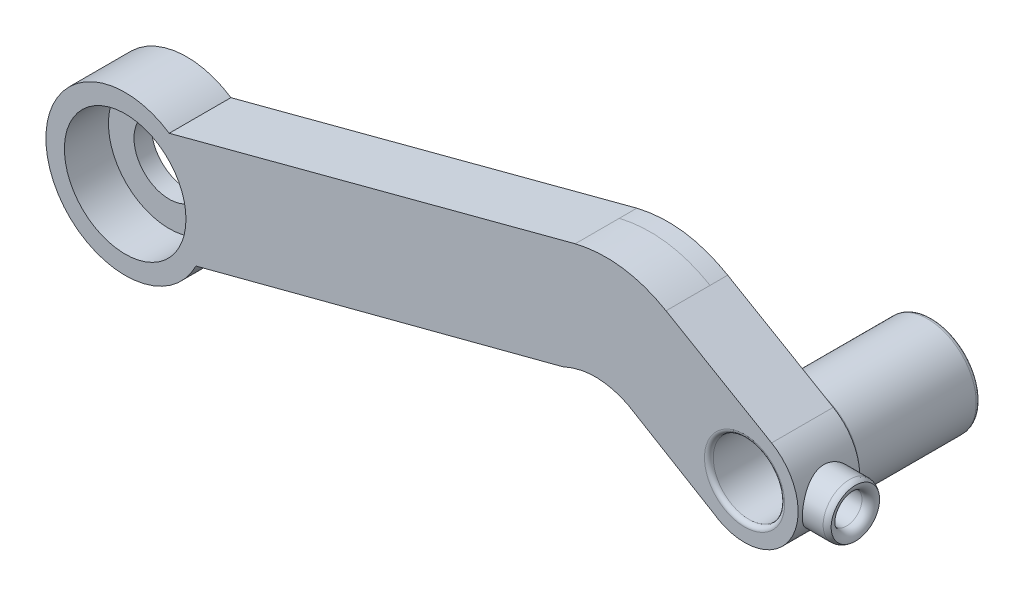
SolidWorks part; units mm, degrees
ref_plane "Front Plane" through (0, 0, 0) normal (0, 0, 1) x (1, 0, 0)
ref_plane "Top Plane" through (0, 0, 0) normal (0, 1, 0) x (1, 0, 0)
ref_plane "Right Plane" through (0, 0, 0) normal (1, 0, 0) x (0, 0, -1)
sketch "Sketch2" plane through (0, 0, 102.4316) normal (0, 0, 1) x (1, 0, 0)
  line L8 (-120.223, 48.1324) -> (-110.6681, 42.4279)
  line L9 (-169.3666, 37.3143) -> (-127.7161, 48.234)
  line L10 (-126.3187, 61.0272) -> (-172.4039, 48.8476)
  line L11 (-104.0278, 52.5928) -> (-116.0098, 59.5925)
  circle A2 centre (-107.0939, 47.3443) radius 4.05
  circle A3 centre (-177.4038, 41.3642) radius 6.9
  arc A5 (-110.6681, 42.4279) -> (-104.0278, 52.5928) centre (-107.0939, 47.3443) ccw
  arc A6 (-172.4039, 48.8476) -> (-169.3666, 37.3143) centre (-177.4038, 41.3642) ccw
  parabola Q4 (-127.7161, 48.234) -> (-120.223, 48.1324) focus (-123.8474, 45.2368) apex (-123.6641, 49.0843)
  parabola Q5 (-116.0098, 59.5925) -> (-126.3187, 61.0272) focus (-121.5094, 54.8565) apex (-120.2687, 61.2162)
extrude "Boss-Extrude1" add sketch "Sketch2" along normal blind 5
sketch "Sketch3" plane through (0, 0, 102.4316) normal (0, 0, -1) x (-1, 0, 0)
  line L4 (110.6681, 42.4279) -> (120.223, 48.1324)
  line L5 (127.7161, 48.234) -> (169.3666, 37.3143)
  line L6 (172.4039, 48.8476) -> (126.3187, 61.0272)
  line L7 (116.0098, 59.5925) -> (104.0278, 52.5928)
  line L8 (110.6681, 42.4279) -> (120.223, 48.1324)
  line L9 (127.7161, 48.234) -> (169.3666, 37.3143)
  line L10 (172.4039, 48.8476) -> (126.3187, 61.0272)
  line L11 (116.0098, 59.5925) -> (104.0278, 52.5928)
  circle A0 centre (107.0939, 47.3443) radius 4.05
  circle A1 centre (177.4038, 41.3642) radius 4
  arc A2 (104.0278, 52.5928) -> (110.6681, 42.4279) centre (107.0939, 47.3443) ccw
  arc A3 (169.3666, 37.3143) -> (172.4039, 48.8476) centre (177.4038, 41.3642) ccw
  arc A4 (104.0278, 52.5928) -> (110.6681, 42.4279) centre (107.0939, 47.3443) ccw
  arc A5 (169.3666, 37.3143) -> (172.4039, 48.8476) centre (177.4038, 41.3642) ccw
  parabola Q2 (120.223, 48.1324) -> (127.7161, 48.234) focus (123.8474, 45.2368) apex (123.6641, 49.0843)
  parabola Q3 (126.3187, 61.0272) -> (116.0098, 59.5925) focus (121.5094, 54.8565) apex (120.2687, 61.2162)
  parabola Q4 (120.223, 48.1324) -> (127.7161, 48.234) focus (123.8474, 45.2368) apex (123.6641, 49.0843)
  parabola Q5 (126.3187, 61.0272) -> (116.0098, 59.5925) focus (121.5094, 54.8565) apex (120.2687, 61.2162)
  dimension "D2" = 8.1
  dimension "D3" = 8
  dimension "D1" = 0
extrude "Boss-Extrude2" add sketch "Sketch3" along normal blind 2
sketch "Sketch5" plane through (0, 0, 100.4316) normal (0, 0, -1) x (-1, 0, 0)
  circle A0 centre (107.0939, 47.3443) radius 5.5
  circle A1 centre (107.0939, 47.3443) radius 4.05
  dimension "D1" = 11
  dimension "D2" = 8.1
extrude "Boss-Extrude3" add sketch "Sketch5" along normal blind 11.3
sketch "Sketch6" plane through (0, 0, 89.1316) normal (0, 0, -1) x (-1, 0, 0)
  circle A0 centre (107.0939, 47.3443) radius 5.5
  circle A1 centre (107.0939, 47.3443) radius 5.5 construction
  circle A2 centre (107.0939, 47.3443) radius 2.75
  dimension "D1" = 5.5
extrude "Boss-Extrude4" add sketch "Sketch6" along normal blind 3
fillet "Fillet1" radius 0.5 1 edges at (-112.5939, 47.3443, 100.4316)
fillet "Fillet2" radius 0.5 1 edges at (-112.5939, 47.3443, 86.1316)
fillet "Fillet3" radius 0.5 3 edges at (-103.0439, 47.3443, 107.4316) (-109.8439, 47.3443, 86.1316) (-109.8439, 47.3443, 89.1316)
ref_plane "Plane1" through (-101.0155, 0, 0) normal (1, 0, 0) x (0, 0, -1)
sketch "Sketch7" plane through (-101.0155, 0, 0) normal (1, 0, 0) x (0, 0, -1)
  circle A0 centre (-103.9316, 46.9294) radius 3
  dimension "D1" = 6
extrude "Boss-Extrude5" add sketch "Sketch7" along normal blind 3 and the other way blind 1
sketch "Sketch8" plane through (-98.0155, 0, 0) normal (1, 0, 0) x (0, 0, -1)
  circle A0 centre (-103.9316, 46.9294) radius 1.75
  dimension "D1" = 3.5
extrude "Cut-Extrude1" cut sketch "Sketch8" against normal blind 8
fillet "Fillet4" radius 1 1 edges at (-98.0155, 46.9294, 102.1816)
fillet "Fillet5" radius 1 1 edges at (-98.0155, 46.9294, 100.9316)
